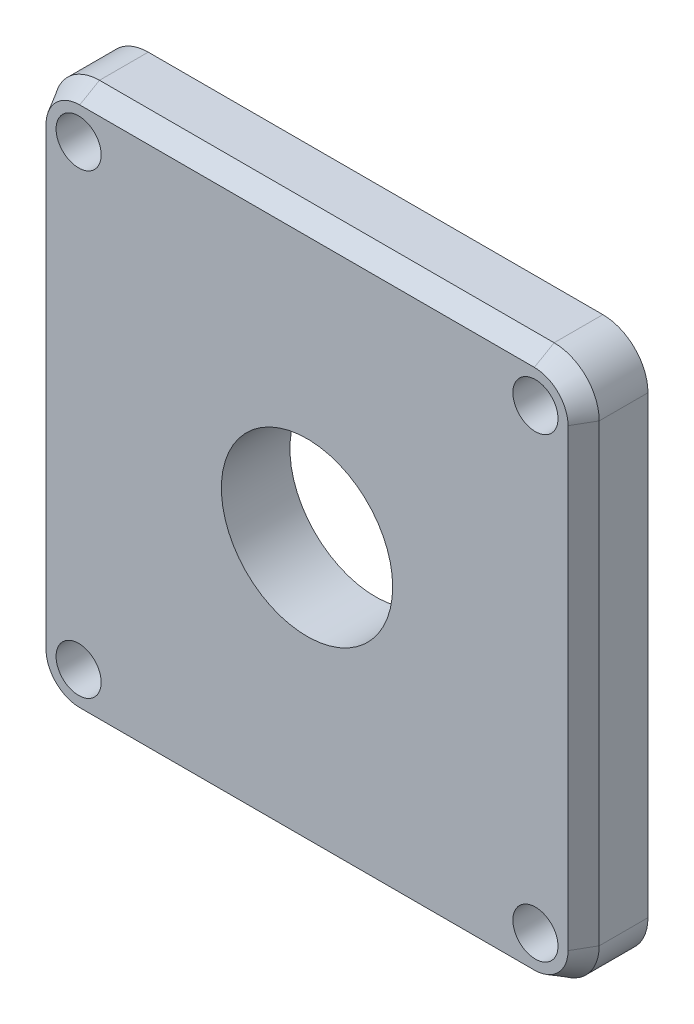
SolidWorks part; units mm, degrees
ref_plane "Plan de face" through (0, 0, 0) normal (0, 0, 1) x (1, 0, 0)
ref_plane "Plan de dessus" through (0, 0, 0) normal (0, 1, 0) x (1, 0, 0)
ref_plane "Plan de droite" through (0, 0, 0) normal (1, 0, 0) x (0, 0, -1)
sketch "Esquisse1" plane through (0, 0, 0) normal (0, 0, 1) x (1, 0, 0)
  line L1 (-47.7075, -47.7075) -> (47.7075, -47.7075)
  line L2 (-47.7075, -47.7075) -> (-47.7075, 47.7075)
  line L3 (-47.7075, 47.7075) -> (47.7075, 47.7075)
  line L4 (47.7075, -47.7075) -> (47.7075, 47.7075)
  line L5 (-47.7075, -47.7075) -> (47.7075, 47.7075) construction
  line L6 (-47.7075, 47.7075) -> (47.7075, -47.7075) construction
  circle A0 centre (0, 0) radius 15
  circle A1 centre (-40, 40) radius 3.95
  circle A2 centre (40, 40) radius 3.95
  circle A3 centre (40, -40) radius 3.95
  circle A4 centre (-40, -40) radius 3.95
  dimension "D1" = 30
  dimension "D2" = 7.9
  dimension "D4" = 10.9
  dimension "D3" = 80
extrude "Boss.-Extru.1" add sketch "Esquisse1" along normal blind 2 contours A1 | A2 | A3 | A4 | L1 L4 L3 L2 A4 A3 A2 A1 A0 region at (-46.3581, 0, 0) region at (-40, 40, 0) region at (40, 40, 0) region at (40, -40, 0) region at (-40, -40, 0)
extrude "Boss.-Extru.2" add sketch "Esquisse1<3>" along normal blind 10 from surface starting at face at (15, 0, 2)
sketch "Esquisse1<3>" plane through (0, 0, 0) normal (0, 0, 1) x (1, 0, 0) same geometry as "Esquisse1"
fillet "Congé1" radius 7.9 4 edges at (47.7075, 47.7075, 6) (47.7075, -47.7075, 6) (-47.7075, -47.7075, 6) (-47.7075, 47.7075, 6)
chamfer "Chanfrein1" distance 2 angle 60 8 edges at (0, 47.7075, 12) (45.3936, 45.3936, 12) (-45.3936, 45.3936, 12) (47.7075, 0, 12) (-47.7075, 0, 12) (45.3936, -45.3936, 12) (-45.3936, -45.3936, 12) (0, -47.7075, 12) first distance on face at (0, 0, 12)
sketch "Esquisse4" plane through (0, 0, 0) normal (0, 0, -1) x (-1, 0, 0)
  line L1 (30, -30) -> (-30, -30) construction
  line L2 (30, -30) -> (30, 30) construction
  line L3 (30, 30) -> (-30, 30) construction
  line L4 (-30, -30) -> (-30, 30) construction
  line L5 (30, -30) -> (-30, 30) construction
  line L6 (30, 30) -> (-30, -30) construction
  circle A0 centre (-30, 30) radius 3.15
  circle A1 centre (-30, -30) radius 3.15
  circle A2 centre (30, -30) radius 3.15
  circle A3 centre (30, 30) radius 3.15
  point P2 (0, 0)
  dimension "D1" = 6.3
  dimension "D2" = 60
extrude "Enlèv. mat.-Extru.2" cut sketch "Esquisse4" against normal blind 8
